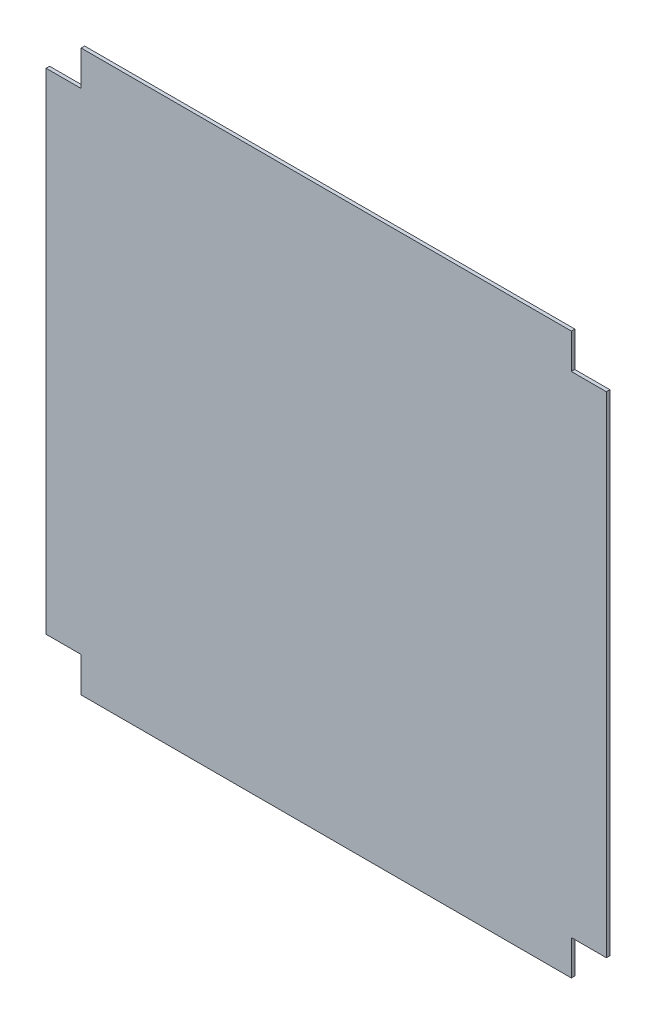
SolidWorks part; units mm, degrees
material "6063-T1"
ref_plane "Front Plane" through (0, 0, 0) normal (1, 0, 0) x (0, 1, 0)
ref_plane "Top Plane" through (0, 0, 0) normal (0, 0, 1) x (0, 1, 0)
ref_plane "Right Plane" through (0, 0, 0) normal (0, 1, 0) x (-1, 0, 0)
sketch "Sketch1" plane through (0, 0, 0) normal (0, 0, 1) x (0, 1, 0)
  line L0 (300, 0) -> (320, 0)
  line L1 (0, 0) -> (320, 0)
  line L2 (0, 0) -> (0, -320)
  line L3 (0, -320) -> (320, -320)
  line L4 (320, 0) -> (320, -320)
  line L5 (0, 0) -> (20, 0)
  line L6 (0, 0) -> (0, -20)
  line L7 (0, -20) -> (20, -20)
  line L8 (20, 0) -> (20, -20)
  line L9 (300, 0) -> (300, -20)
  line L10 (300, -20) -> (320, -20)
  line L11 (320, 0) -> (320, -20)
  line L12 (300, -300) -> (320, -300)
  line L13 (300, -300) -> (300, -320)
  line L14 (300, -320) -> (320, -320)
  line L15 (320, -300) -> (320, -320)
  line L16 (0, -300) -> (20, -300)
  line L17 (0, -300) -> (0, -320)
  line L18 (0, -320) -> (20, -320)
  line L19 (20, -300) -> (20, -320)
  line L20 (0, 0) -> (300, 0) construction
  line L21 (0, 0) -> (0, -300) construction
  dimension "D1" = 320
  dimension "D2" = 320
  dimension "D4" = 20
  dimension "D3" = 20
  dimension "D7" = 300
  dimension "D8" = 300
  dimension "D5" = 2
  dimension "D6" = 2
extrude "Boss-Extrude1" add sketch "Sketch1" along normal blind 2 contours L16 L19 L3 L13 L12 L4 L10 L9 L1 L8 L7 L2 region at (160, 160, 0)
equation "\"extrusion_width\"= 20mm"
equation "\"frame_height\"= 360mm"
equation "\"frame_width\"= 320mm"
equation "\"frame_length\"= 320mm"
equation "\"D1@Sketch1\"=\"frame_length\""
equation "\"D2@Sketch1\"=\"frame_width\""
equation "\"D3@Sketch1\"=\"extrusion_width\""
equation "\"D7@Sketch1\"=\"frame_length\"-\"extrusion_width\""
equation "\"D8@Sketch1\"=\"frame_width\"-\"extrusion_width\""
equation "\"base_platform_thickness\"= 2mm'depends on sheet metal"
equation "\"D1@Boss-Extrude1\"=\"base_platform_thickness\""
